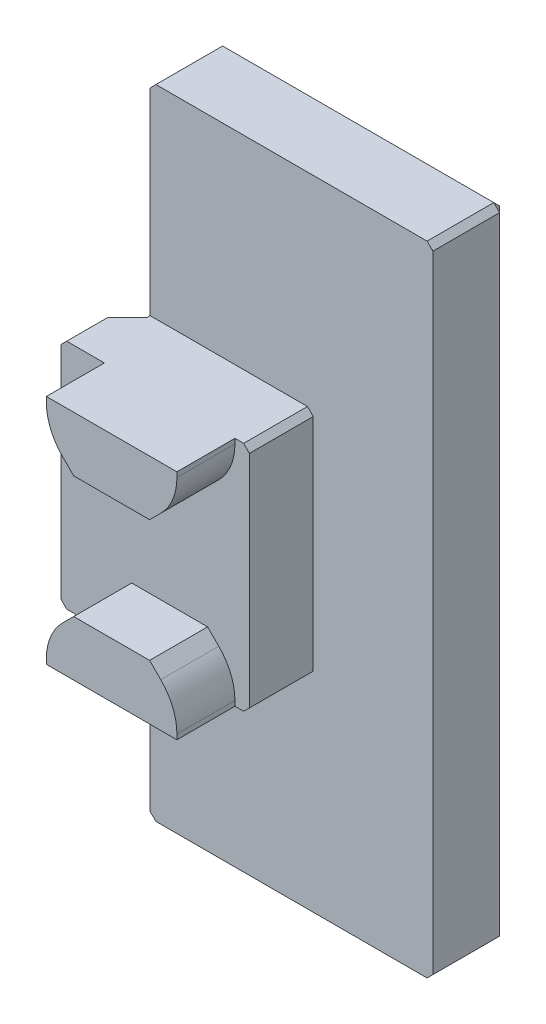
SolidWorks part; units mm, degrees
ref_plane "Front" through (0, 0, 0) normal (0, 0, 1) x (1, 0, 0)
ref_plane "Top" through (0, 0, 0) normal (0, 1, 0) x (1, 0, 0)
ref_plane "Right" through (0, 0, 0) normal (1, 0, 0) x (0, 0, -1)
sketch "Sketch1" plane through (0, 0, 0) normal (0, 0, 1) x (1, 0, 0)
  line L0 (-2.75, -11) -> (-2.75, -4.5) construction
  line L1 (2.75, -4) -> (-2.75, -4)
  line L2 (2.75, -4) -> (2.75, 4)
  line L3 (2.75, 4) -> (-2.75, 4)
  line L4 (-2.75, -4) -> (-2.75, 4) construction
  line L5 (2.75, -4) -> (-2.75, 4) construction
  line L6 (2.75, 4) -> (-2.75, -4) construction
  line L7 (-2.35, -4) -> (-3.75, -4) construction
  line L8 (-2.75, 4) -> (-3.75, 4)
  line L9 (-3.75, 4) -> (-3.75, -4)
  line L10 (-3.75, -4) -> (-2.75, -4)
  point P0 (0, 0)
extrude "Boss-Extrude1" add sketch "Sketch1" against normal blind 2
sketch "Sketch2" plane through (0, 0, 0) normal (0, 0, 1) x (1, 0, 0)
  line L0 (-2.25, -3.8284) -> (-2.25, -4)
  line L1 (-1.6935, -6.0151) -> (-1.3086, -6.4) construction
  line L2 (-1.3086, -6.4) -> (1.3086, -6.4) construction
  line L3 (1.3086, -6.4) -> (1.6935, -6.0151) construction
  line L4 (2.25, -4.6716) -> (2.25, -3.8284) construction
  line L5 (1.6935, -2.4849) -> (1.3086, -2.1)
  line L6 (1.3086, -2.1) -> (-1.3086, -2.1)
  line L7 (-1.3086, -2.1) -> (-1.6935, -2.4849)
  line L8 (-2.25, -3.8284) -> (-2.25, -4.6716) construction
  line L9 (1.35, -6.5) -> (1.7642, -6.0858)
  line L10 (-1.35, -6.5) -> (1.35, -6.5)
  line L11 (-1.7642, -6.0858) -> (-1.35, -6.5)
  line L12 (-2.35, -3.8284) -> (-2.35, -4.6716)
  line L13 (-1.35, -2) -> (-1.7642, -2.4142)
  line L14 (1.35, -2) -> (-1.35, -2)
  line L15 (1.7642, -2.4142) -> (1.35, -2)
  line L16 (2.35, -4.6716) -> (2.35, -3.8284)
  line L17 (1.35, -6.5) -> (1.7642, -6.0858) construction
  line L18 (-1.35, -6.5) -> (1.35, -6.5) construction
  line L20 (-1.7642, -6.0858) -> (-1.35, -6.5) construction
  line L22 (-2.35, -3.8284) -> (-2.35, -4.6716) construction
  line L24 (-1.35, -2) -> (-1.7642, -2.4142) construction
  line L26 (1.35, -2) -> (-1.35, -2) construction
  line L28 (1.7642, -2.4142) -> (1.35, -2) construction
  line L30 (2.35, -4.6716) -> (2.35, -3.8284) construction
  line L32 (2.25, -3.8284) -> (2.25, -4)
  line L39 (-2.75, -4) -> (2.75, -4)
  line L40 (-3.75, -4) -> (-2.75, -4)
  line L41 (-3.75, 4) -> (-3.75, -4)
  line L46 (-2.75, 4) -> (-3.75, 4)
  line L48 (2.75, 4) -> (-2.75, 4)
  line L54 (2.75, -4) -> (2.75, 4)
  line L58 (-2.25, -4) -> (2.25, -4)
  arc A0 (-2.25, -4.6716) -> (-1.6935, -6.0151) centre (-0.35, -4.6716) ccw construction
  arc A2 (1.6935, -6.0151) -> (2.25, -4.6716) centre (0.35, -4.6716) ccw construction
  arc A4 (2.25, -3.8284) -> (1.6935, -2.4849) centre (0.35, -3.8284) ccw
  arc A5 (-1.6935, -2.4849) -> (-2.25, -3.8284) centre (-0.35, -3.8284) ccw
  arc A7 (-2.35, -4.6716) -> (-1.7642, -6.0858) centre (-0.35, -4.6716) ccw
  arc A8 (-1.7642, -2.4142) -> (-2.35, -3.8284) centre (-0.35, -3.8284) ccw
  arc A10 (2.35, -3.8284) -> (1.7642, -2.4142) centre (0.35, -3.8284) ccw
  arc A11 (1.7642, -6.0858) -> (2.35, -4.6716) centre (0.35, -4.6716) ccw
  arc A12 (-2.35, -4.6716) -> (-1.7642, -6.0858) centre (-0.35, -4.6716) ccw construction
  arc A13 (-1.7642, -2.4142) -> (-2.35, -3.8284) centre (-0.35, -3.8284) ccw construction
  arc A14 (2.35, -3.8284) -> (1.7642, -2.4142) centre (0.35, -3.8284) ccw construction
  arc A15 (1.7642, -6.0858) -> (2.35, -4.6716) centre (0.35, -4.6716) ccw construction
  dimension "D1" = 0
  dimension "D2" = 0.1
  dimension "D3" = 0
extrude "Slot Tab" add sketch "Sketch2" along normal blind 2 contours L7 A5 L0 L58 L32 A4 L5 L6 region at (0, -3.1243, 0)
mirror "Slot Tabs" about plane through (0, 0, 0) normal (0, 1, 0) of "Slot Tab"
chamfer "Deburs" [suppressed] distance 0.2 angle 45
sketch "Sketch3" plane through (0, 0, -2) normal (0, 0, -1) x (-1, 0, 0)
  line L4 (3.75, 4) -> (-2.75, 4)
  line L5 (-2.75, 4) -> (-2.75, -4)
  line L6 (-2.75, -4) -> (3.75, -4)
  line L7 (3.75, -4) -> (3.75, 4)
  line L8 (3.75, 4) -> (-2.75, 4)
  line L9 (-2.75, 4) -> (-2.75, -4)
  line L10 (-2.75, -4) -> (3.75, -4)
  line L11 (3.75, -4) -> (3.75, 4)
  dimension "D1" = 0
extrude "Stopper Clearance" add sketch "Sketch3" along normal blind 0.2
sketch "Sketch4" plane through (0, 0, -2.2) normal (0, 0, -1) x (-1, 0, 0)
  line L1 (2.875, -11) -> (-6.875, -11)
  line L2 (2.875, -11) -> (2.875, 11)
  line L3 (2.875, 11) -> (-6.875, 11)
  line L4 (-6.875, -11) -> (-6.875, 11)
  line L5 (2.875, -11) -> (-6.875, 11) construction
  line L6 (2.875, 11) -> (-6.875, -11) construction
  point P0 (-2, 0)
  point P5 (2.75, 11)
  dimension "D1" = 2
  dimension "D2" = 22
  dimension "D3" = 9.75
extrude "Stopper" add sketch "Sketch4" along normal blind 2.5
chamfer "Deburs 2" distance 0.2 angle 45 12 edges at (2.75, 4, -1.1) (2.75, -4, -1.1) (-3.75, -4, -1.1) (-3.75, 4, -1.1) (2, 11, -4.7) (-2.875, 11, -3.45) (-2.875, 0, -4.7) (6.875, 11, -3.45) (6.875, 0, -4.7) (6.875, -11, -3.45) (2, -11, -4.7) (-2.875, -11, -3.45)
chamfer "Chamfer3" distance 1 angle 45 1 edges at (-3.75, 0, -2.2)
